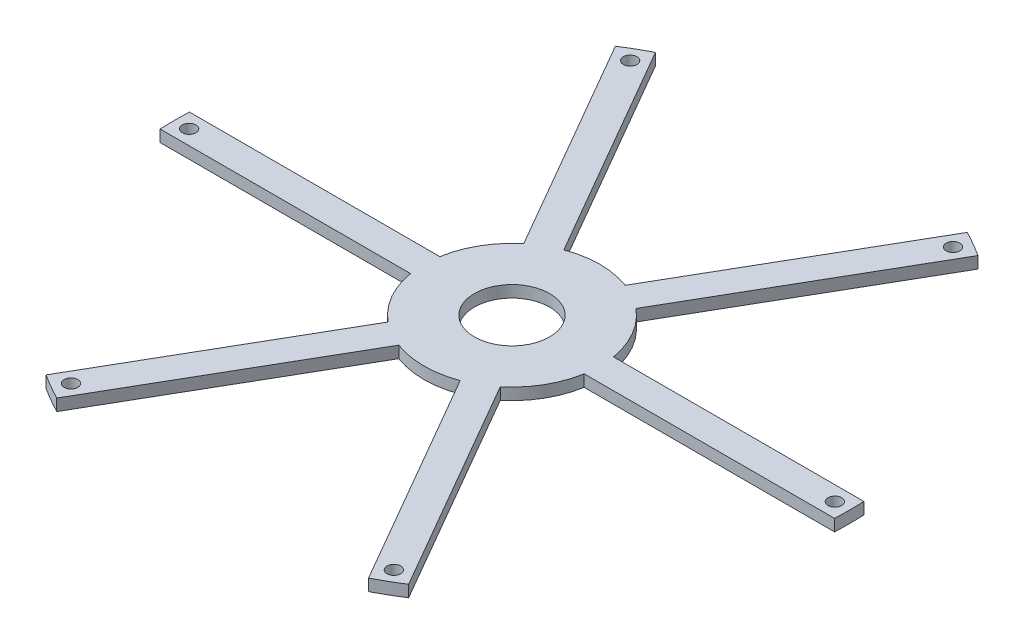
SolidWorks part; units mm, degrees
ref_plane "Front Plane" through (0, 0, 0) normal (0, 0, 1) x (1, 0, 0)
ref_plane "Top Plane" through (0, 0, 0) normal (0, 1, 0) x (1, 0, 0)
ref_plane "Right Plane" through (0, 0, 0) normal (1, 0, 0) x (0, 0, -1)
sketch "Sketch1" plane through (0, 0, 0) normal (0, 1, 0) x (1, 0, 0)
  line L0 (0, 0) -> (72.9559, 0) construction
  line L1 (18.7836, 3.175) -> (72.9559, 3.175)
  line L3 (18.7836, -3.175) -> (72.9559, -3.175)
  line L4 (72.9559, 3.175) -> (72.9559, -3.175) construction
  line L5 (12.1414, -14.6795) -> (39.2276, -61.5942)
  line L7 (6.6421, -17.8545) -> (33.7283, -64.7692)
  line L8 (39.2276, -61.5942) -> (33.7283, -64.7692) construction
  line L9 (-6.6421, -17.8545) -> (-33.7283, -64.7692)
  line L11 (-12.1414, -14.6795) -> (-39.2276, -61.5942)
  line L12 (-33.7283, -64.7692) -> (-39.2276, -61.5942) construction
  line L13 (-18.7836, -3.175) -> (-72.9559, -3.175)
  line L15 (-18.7836, 3.175) -> (-72.9559, 3.175)
  line L16 (-72.9559, -3.175) -> (-72.9559, 3.175) construction
  line L17 (-12.1414, 14.6795) -> (-39.2276, 61.5942)
  line L19 (-6.6421, 17.8545) -> (-33.7283, 64.7692)
  line L20 (-39.2276, 61.5942) -> (-33.7283, 64.7692) construction
  line L21 (6.6421, 17.8545) -> (33.7283, 64.7692)
  line L23 (12.1414, 14.6795) -> (39.2276, 61.5942)
  line L24 (33.7283, 64.7692) -> (39.2276, 61.5942) construction
  arc A0 (39.2276, 61.5942) -> (33.7283, 64.7692) centre (0, 0) ccw
  arc A1 (-12.1414, 14.6795) -> (-18.7836, 3.175) centre (0, 0) ccw
  arc A2 (6.6421, 17.8545) -> (-6.6421, 17.8545) centre (0, 0) ccw
  arc A3 (-18.7836, -3.175) -> (-12.1414, -14.6795) centre (0, 0) ccw
  arc A4 (-6.6421, -17.8545) -> (6.6421, -17.8545) centre (0, 0) ccw
  arc A5 (12.1414, -14.6795) -> (18.7836, -3.175) centre (0, 0) ccw
  arc A6 (18.7836, 3.175) -> (12.1414, 14.6795) centre (0, 0) ccw
  arc A7 (-33.7283, 64.7692) -> (-39.2276, 61.5942) centre (0, 0) ccw
  arc A8 (-72.9559, 3.175) -> (-72.9559, -3.175) centre (0, 0) ccw
  arc A9 (-39.2276, -61.5942) -> (-33.7283, -64.7692) centre (0, 0) ccw
  arc A10 (33.7283, -64.7692) -> (39.2276, -61.5942) centre (0, 0) ccw
  arc A11 (72.9559, -3.175) -> (72.9559, 3.175) centre (0, 0) ccw
  point P31 (0, 0)
  dimension "D1" = 146.05
  dimension "D2" = 38.1
  dimension "D3" = 6.35
  dimension "D4" = 6
extrude "Boss-Extrude1" add sketch "Sketch1" along normal blind 2.54
hole_wizard "5/8 Clearance Hole1" positions "Sketch3" profile "Sketch2" hole size "5/8" standard "ANSI Inch"
sketch "Sketch3" plane through (0, 2.54, 0) normal (0, 1, 0) x (1, 0, 0)
  point P0 (0, 0)
sketch "Sketch2" plane through (0, 2.54, 0) normal (1, 0, 0) x (0, 0, 1)
  line L0 (0, 0) -> (0, 43.2424)
  line L1 (0, 43.2424) -> (8.1356, 38.354)
  line L2 (8.1356, 38.354) -> (8.1356, 0)
  line L5 (8.1356, 0) -> (0, 0)
  line L10 (0, 43.2424) -> (-8.1356, 38.354) construction
  line L11 (0, -6.35) -> (0, 107.95) construction
  dimension "Hole Dia." = 16.2712
  dimension "Hole Depth" = 38.354
  dimension "Drill Angle" = 118
hole_wizard "#4 Clearance Hole1" positions "Sketch6" profile "Sketch4" hole size "#4" standard "ANSI Inch"
sketch "Sketch6" plane through (0, 2.54, 0) normal (0, 1, 0) x (1, 0, 0)
  line L0 (-73.025, 0) -> (-52.9675, 0) construction
  line L3 (0, 0) -> (-69.85, 0) construction
  arc A0 (-72.9559, 3.175) -> (-72.9559, -3.175) centre (0, 0) ccw construction
  point P0 (-69.85, 0)
  point P40 (-34.925, 60.4919)
  point P41 (34.925, 60.4919)
  point P42 (69.85, 0)
  point P43 (34.925, -60.4919)
  point P44 (-34.925, -60.4919)
  dimension "D1" = 69.85
  dimension "D3" = 69.85
  dimension "D2" = 6
sketch "Sketch4" plane through (-69.85, 2.54, 0) normal (1, 0, 0) x (0, 0, 1)
  line L0 (0, 0) -> (0, 39.2392)
  line L1 (0, 39.2392) -> (1.4732, 38.354)
  line L2 (1.4732, 38.354) -> (1.4732, 0)
  line L5 (1.4732, 0) -> (0, 0)
  line L10 (0, 39.2392) -> (-1.4732, 38.354) construction
  line L11 (0, -6.35) -> (0, 107.95) construction
  dimension "Hole Dia." = 2.9464
  dimension "Hole Depth" = 38.354
  dimension "Drill Angle" = 118
